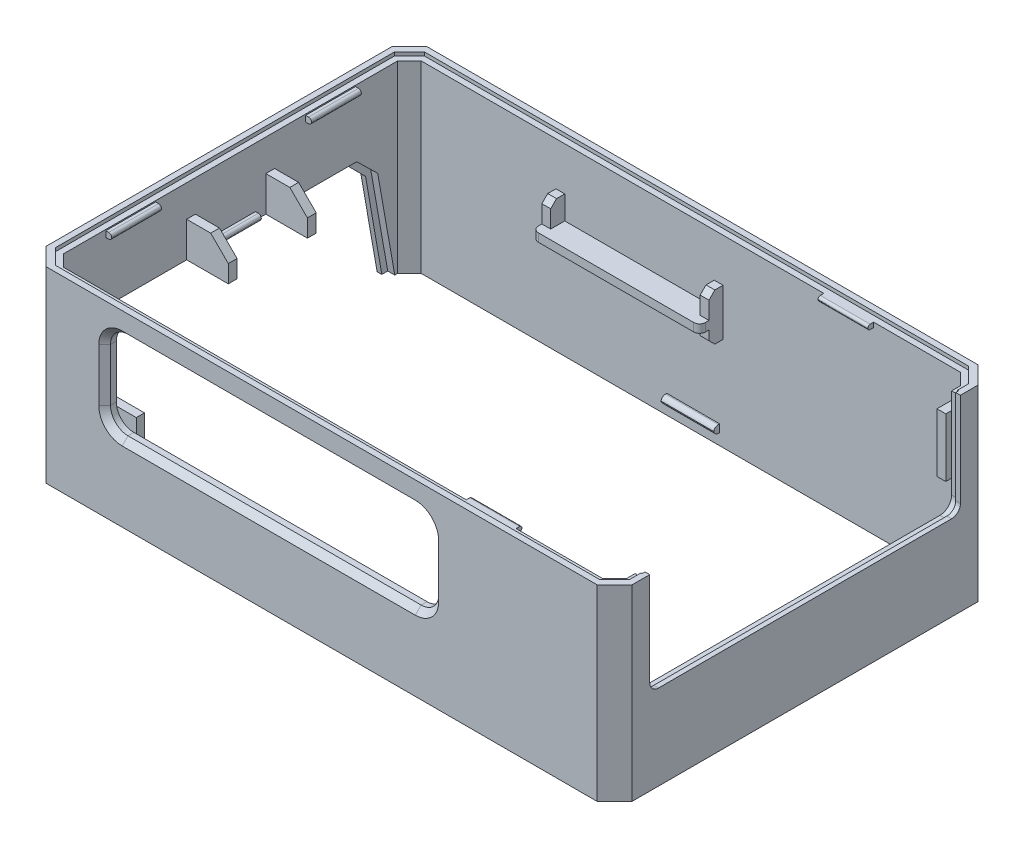
SolidWorks part; units mm, degrees
ref_plane "前视基准面" through (0, 0, 0) normal (0, 0, 1) x (1, 0, 0)
ref_plane "上视基准面" through (0, 0, 0) normal (0, 1, 0) x (1, 0, 0)
ref_plane "右视基准面" through (0, 0, 0) normal (1, 0, 0) x (0, 0, -1)
sketch "草图1" plane through (0, 0, 0) normal (0, 1, 0) x (1, 0, 0)
  line L1 (-50, 32.5) -> (50, 32.5)
  line L2 (-50, 32.5) -> (-50, -32.5)
  line L3 (-50, -32.5) -> (50, -32.5)
  line L4 (50, 32.5) -> (50, -32.5)
  line L5 (-50, 32.5) -> (50, -32.5) construction
  line L6 (-50, -32.5) -> (50, 32.5) construction
  point P0 (0, 0)
  dimension "D1" = 65
  dimension "D2" = 100
extrude "凸台-拉伸1" add sketch "草图1" along normal blind 32
sketch "草图2" plane through (0, 32, 0) normal (0, 1, 0) x (1, 0, 0)
  line L8 (48, -30.5) -> (48, 30.5)
  line L9 (48, 30.5) -> (-48, 30.5)
  line L10 (-48, 30.5) -> (-48, -30.5)
  line L11 (-48, -30.5) -> (48, -30.5)
  line L12 (48, -30.5) -> (48, 30.5)
  line L13 (48, 30.5) -> (-48, 30.5)
  line L14 (-48, 30.5) -> (-48, -30.5)
  line L15 (-48, -30.5) -> (48, -30.5)
  dimension "D1" = 2
extrude "切除-拉伸1" cut sketch "草图2" against normal through all
sketch "草图4" plane through (-50, 0, 0) normal (-1, 0, 0) x (0, 0, 1)
  line L0 (-32.5, 0) -> (32.5, 0) construction
  line L3 (-28, 0) -> (28, 0)
  line L7 (-25.0863, 16.5) -> (-21.5, 20)
  line L8 (21.5, 20) -> (25.09, 16.5)
  line L9 (32.5, 32) -> (32.5, 0) construction
  line L12 (-25.0863, 16.5) -> (-28, 0)
  line L13 (-21.5, 20) -> (21.5, 20)
  line L14 (25.09, 16.5) -> (28, 0)
  line L15 (-32.5, 0) -> (32.5, 0) construction
  line L16 (-32.5, 32) -> (-32.5, 0) construction
  dimension "D1" = 16.5
  dimension "D2" = 20
  dimension "D3" = 4.5
  dimension "D4" = 4.5
  dimension "D5" = 11
  dimension "D6" = 11
  dimension "D7" = 7.4137
  dimension "D8" = 7.41
extrude "切除-拉伸2" cut sketch "草图4" against normal blind 2
sketch "草图7" plane through (0, 0, 32.5) normal (0, 0, 1) x (1, 0, 0)
  line L16 (-37, 28) -> (-37, 13)
  line L17 (19, 28) -> (-37, 28)
  line L18 (19, 13) -> (19, 28)
  line L19 (-37, 13) -> (19, 13)
extrude "切除-拉伸3" cut sketch "草图7" against normal blind 2.5
fillet "圆角7" radius 3 4 edges at (-37, 28, 31.5) (19, 28, 31.5) (19, 13, 31.5) (-37, 13, 31.5)
chamfer "倒角1" distance 1 angle 45 8 edges at (-9, 28, 32.5) (-36.1213, 27.1213, 32.5) (18.1213, 27.1213, 32.5) (-37, 20.5, 32.5) (19, 20.5, 32.5) (-36.1213, 13.8787, 32.5) (18.1213, 13.8787, 32.5) (-9, 13, 32.5)
sketch "草图9" plane through (50, 0, 0) normal (1, 0, 0) x (0, 0, -1)
  line L0 (-25.6851, 37.094) -> (-12.3808, 37.094)
  line L1 (-25.6851, 37.094) -> (-25.6851, 22.8739)
  line L2 (-25.6851, 22.8739) -> (-12.3808, 22.8739)
  line L3 (-12.3808, 37.094) -> (-12.3808, 22.8739)
  line L4 (-7.5808, 37.094) -> (5.5192, 37.094)
  line L5 (-7.5808, 37.094) -> (-7.5808, 22.8739)
  line L6 (-7.5808, 22.8739) -> (5.5192, 22.8739)
  line L7 (5.5192, 37.094) -> (5.5192, 22.8739)
  line L8 (10, 33.8806) -> (25.4692, 33.8806)
  line L9 (10, 33.8806) -> (10, 21.8806)
  line L10 (10, 21.8806) -> (25.4692, 21.8806)
  line L11 (25.4692, 33.8806) -> (25.4692, 21.8806)
  line L14 (-32.5, 32) -> (-32.5, 0) construction
  line L15 (32.5, 32) -> (32.5, 0) construction
  dimension "D1" = 14.2201
  dimension "D2" = 13.1
  dimension "D3" = 6.8149
  dimension "D4" = 24.9192
  dimension "D5" = 7.0308
  dimension "D6" = 12
ref_plane "基准面4" through (0, 19.25, 0) normal (0, -1, 0) x (-1, 0, 0)
sketch "草图10" plane through (0, 19.25, 0) normal (0, -1, 0) x (-1, 0, 0)
  line L0 (-41.8403, 31.4577) -> (-41.8403, -31.3544)
sketch "草图11" plane through (48, 0, 0) normal (-1, 0, 0) x (0, 0, 1)
  line L1 (-8.8, 24.925) -> (-7.3, 24.925)
  line L2 (-8.8, 24.925) -> (-8.8, 19.925)
  line L3 (-8.8, 19.925) -> (-7.3, 19.925)
  line L4 (-7.3, 24.925) -> (-7.3, 19.925)
  line L5 (32.5, 32) -> (25.6851, 32) construction
  line L6 (9, 24.925) -> (10.5, 24.925)
  line L7 (9, 24.925) -> (9, 19.925)
  line L8 (9, 19.925) -> (10.5, 19.925)
  line L9 (10.5, 24.925) -> (10.5, 19.925)
  line L11 (32.5, 32) -> (32.5, 0) construction
  line L12 (-32.5, 32) -> (-32.5, 0) construction
  dimension "D1" = 1.5
  dimension "D2" = 1.5
  dimension "D3" = 22
  dimension "D4" = 23.7
  dimension "D5" = 5
  dimension "D6" = 12.075
sketch "草图17" plane through (-48, 0, 0) normal (1, 0, 0) x (0, 0, -1)
  line L1 (-6, 20) -> (-7.5, 20)
  line L2 (-6, 20) -> (-6, 26)
  line L3 (-6, 26) -> (-7.5, 26)
  line L4 (-7.5, 20) -> (-7.5, 26)
  line L5 (32.5, 32) -> (32.5, 0) construction
  line L6 (6, 20) -> (7.5, 20)
  line L7 (6, 20) -> (6, 26)
  line L8 (6, 26) -> (7.5, 26)
  line L9 (7.5, 20) -> (7.5, 26)
  line L10 (-21.5, 20) -> (21.5, 20) construction
  line L12 (-32.5, 32) -> (-32.5, 0) construction
  dimension "D1" = 1.5
  dimension "D2" = 1.5
  dimension "D3" = 25
  dimension "D4" = 25
  dimension "D5" = 6
extrude "凸台-拉伸6" add sketch "草图17" along normal blind 7.1
chamfer "倒角6" distance 3 angle 45 2 edges at (-40.9, 26, -6.75) (-40.9, 26, 6.75)
sketch "草图24" plane through (48, 0, 0) normal (-1, 0, 0) x (0, 0, 1)
  line L1 (-4.5, 3.3) -> (4.5, 3.3)
  line L2 (-4.5, 3.3) -> (-4.5, 1.8)
  line L3 (-4.5, 1.8) -> (4.5, 1.8)
  line L4 (4.5, 3.3) -> (4.5, 1.8)
  line L5 (-4.5, 3.3) -> (4.5, 1.8) construction
  line L6 (-4.5, 1.8) -> (4.5, 3.3) construction
  line L7 (30.5, 0) -> (-30.5, 0) construction
  line L8 (32.5, 0) -> (-32.5, 0) construction
  point P0 (0, 2.55)
  point P10 (0, 0)
  dimension "D1" = 1.5
  dimension "D2" = 1.8
  dimension "D3" = 9
extrude "凸台-拉伸10" add sketch "草图24" along normal blind 1
fillet "圆角15" radius 0.8 2 edges at (47, 3.3, 0) (47, 1.8, 0)
sketch "草图25" plane through (0, 0, 30.5) normal (0, 0, -1) x (-1, 0, 0)
  line L0 (48, 0) -> (-48, 0) construction
  line L1 (-4.9102, 3.2365) -> (4.0898, 3.2365)
  line L2 (-4.9102, 3.2365) -> (-4.9102, 1.9365)
  line L3 (-4.9102, 1.9365) -> (4.0898, 1.9365)
  line L4 (4.0898, 3.2365) -> (4.0898, 1.9365)
  line L5 (-4.9102, 3.2365) -> (4.0898, 1.9365) construction
  line L6 (-4.9102, 1.9365) -> (4.0898, 3.2365) construction
  line L8 (50, 32) -> (50, 0) construction
  point P0 (-0.4102, 2.5865)
  dimension "D1" = 9
  dimension "D2" = 1.3
  dimension "D3" = 2.5865
  dimension "D4" = 50.4102
extrude "凸台-拉伸11" add sketch "草图25" along normal blind 1
sketch "草图26" plane through (0, 0, -30.5) normal (0, 0, 1) x (1, 0, 0)
  line L4 (-4.0898, 3.2365) -> (-4.0898, 1.9365)
  line L5 (4.9102, 3.2365) -> (-4.0898, 3.2365)
  line L6 (4.9102, 1.9365) -> (4.9102, 3.2365)
  line L7 (-4.0898, 1.9365) -> (4.9102, 1.9365)
  line L8 (-4.0898, 3.2365) -> (-4.0898, 1.9365)
  line L9 (4.9102, 3.2365) -> (-4.0898, 3.2365)
  line L10 (4.9102, 1.9365) -> (4.9102, 3.2365)
  line L11 (-4.0898, 1.9365) -> (4.9102, 1.9365)
  dimension "D1" = 0
extrude "凸台-拉伸12" add sketch "草图26" along normal blind 1
fillet "圆角16" radius 0.8 4 edges at (0.4102, 1.9365, -29.5) (0.4102, 3.2365, -29.5) (0.4102, 1.9365, 29.5) (0.4102, 3.2365, 29.5)
chamfer "倒角7" distance 2 angle 45 4 edges at (-48, 16, -30.5) (-48, 16, 30.5) (48, 16, -30.5) (48, 16, 30.5)
chamfer "倒角8" distance 3 angle 45 4 edges at (-50, 16, 32.5) (-50, 16, -32.5) (50, 16, -32.5) (50, 16, 32.5)
sketch "草图28" plane through (-50, 0, 0) normal (-1, 0, 0) x (0, 0, 1)
  line L27 (-29.3, 22.3393) -> (-29.3, 0)
  line L28 (-29.3, 0) -> (-26.9872, 0)
  line L29 (-26.9872, 0) -> (-24.2154, 15.8784)
  line L30 (-24.2154, 15.8784) -> (-21.1176, 18.9896)
  line L31 (-21.1176, 18.9896) -> (21.1176, 18.9896)
  line L32 (21.1176, 18.9896) -> (24.2152, 15.8784)
  line L33 (24.2152, 15.8784) -> (27.008, 0)
  line L34 (27.008, 0) -> (29.3, 0)
  line L35 (29.3, 0) -> (29.3, 22.3393)
  line L36 (29.3, 22.3393) -> (-29.3, 22.3393)
  line L37 (28.5, 0) -> (-28.5, 0) construction
  line L38 (-29.5, 0) -> (-28, 0) construction
  line L39 (28, 0) -> (29.5, 0) construction
extrude "凸台-拉伸13" add sketch "草图28" against normal blind 0.8
sketch "草图30" plane through (-50, 0, 0) normal (-1, 0, 0) x (0, 0, 1)
  line L20 (27.008, 0) -> (29.5, 0) construction
  line L21 (-29.5, 0) -> (-26.9872, 0) construction
  line L22 (-29.5, 32) -> (-29.5, 0) construction
  line L23 (29.5, 0) -> (29.5, 32) construction
  line L24 (-29.5, 32) -> (29.5, 32) construction
  line L32 (27.58, 0) -> (24.7738, 16.1781)
  line L33 (24.7738, 16.1781) -> (21.3669, 19.6)
  line L34 (21.3669, 19.6) -> (-21.3669, 19.6)
  line L35 (-21.3669, 19.6) -> (-24.7741, 16.1781)
  line L36 (-24.7741, 16.1781) -> (-27.5845, 0)
  dimension "D1" = 1.9155
  dimension "D2" = 1.92
  dimension "D3" = 4.7262
  dimension "D4" = 8.1331
  dimension "D5" = 4.7259
  dimension "D6" = 8.1331
  dimension "D7" = 12.4
  dimension "D8" = 15.8219
sketch "草图35" plane through (48, 0, 0) normal (-1, 0, 0) x (0, 0, 1)
  line L0 (-27, 32) -> (27, 32)
  line L1 (-27, 32) -> (-27, 14)
  line L2 (-27, 14) -> (27, 14)
  line L3 (27, 32) -> (27, 14)
  line L4 (32.5, 0) -> (32.5, 32) construction
  line L5 (-32.5, 32) -> (-32.5, 0) construction
  line L6 (28.5, 32) -> (-28.5, 32) construction
  dimension "D1" = 18
  dimension "D3" = 5.5
  dimension "D4" = 5.5
extrude "切除-拉伸6" cut sketch "草图35" against normal blind 1.2
fillet "圆角17" radius 2 2 edges at (48.6, 14, -27) (48.6, 14, 27)
sketch "草图39" plane through (49.2, 0, 0) normal (-1, 0, 0) x (0, 0, 1)
  line L2 (27, 32) -> (-27, 32) construction
  line L12 (-26.5, 32) -> (-26.5, 16)
  line L13 (-25, 14.5) -> (25, 14.5)
  line L14 (26.5, 16) -> (26.5, 32)
  line L15 (26.5, 32) -> (-26.5, 32)
  arc A6 (-26.5, 16) -> (-25, 14.5) centre (-25, 16) ccw
  arc A7 (25, 14.5) -> (26.5, 16) centre (25, 16) ccw
extrude "切除-拉伸7" cut sketch "草图39" against normal blind 1.2
ref_plane "基准面5" through (-50, 32, 29.5) normal (0.7071, 0, 0.7071) x (0.7071, 0, -0.7071)
sketch "草图42" plane through (-48, 0, 0) normal (1, 0, 0) x (0, 0, -1)
  line L0 (32.5, 0) -> (32.5, 32) construction
  line L1 (12.8, 31.2) -> (21.3, 31.2)
  line L2 (12.8, 31.2) -> (12.8, 30.2)
  line L3 (12.8, 30.2) -> (21.3, 30.2)
  line L4 (21.3, 31.2) -> (21.3, 30.2)
  line L5 (12.8, 31.2) -> (21.3, 30.2) construction
  line L6 (12.8, 30.2) -> (21.3, 31.2) construction
  line L7 (-4.2291, 21.2667) -> (4.2291, 21.2667)
  line L8 (-4.2291, 21.2667) -> (-4.2291, 20.2667)
  line L9 (-4.2291, 20.2667) -> (4.2291, 20.2667)
  line L10 (4.2291, 21.2667) -> (4.2291, 20.2667)
  line L11 (-4.2291, 21.2667) -> (4.2291, 20.2667) construction
  line L12 (-4.2291, 20.2667) -> (4.2291, 21.2667) construction
  line L13 (-32.5, 32) -> (-32.5, 0) construction
  line L14 (28.5, 32) -> (-28.5, 32) construction
  line L15 (-12.8, 30.2) -> (-21.3, 30.2)
  line L16 (-12.8, 30.2) -> (-12.8, 31.2)
  line L17 (-12.8, 31.2) -> (-21.3, 31.2)
  line L18 (-21.3, 30.2) -> (-21.3, 31.2)
  line L19 (-12.8, 30.2) -> (-21.3, 31.2) construction
  line L20 (-12.8, 31.2) -> (-21.3, 30.2) construction
  point P0 (17.05, 30.7)
  point P5 (0, 20.7667)
  point P16 (-17.05, 30.7)
  dimension "D1" = 1
  dimension "D2" = 1
  dimension "D3" = 1.3
  dimension "D4" = 11.2
  dimension "D5" = 8.5
  dimension "D6" = 1
  dimension "D7" = 8.5
  dimension "D8" = 11.2
  dimension "D9" = 1.3
extrude "凸台-拉伸14" add sketch "草图42" along normal blind 1
fillet "圆角18" radius 0.5 6 edges at (-47, 20.2667, 0) (-47, 21.2667, 0) (-47, 30.2, -17.05) (-47, 31.2, -17.05) (-47, 31.2, 17.05) (-47, 30.2, 17.05)
sketch "草图44" plane through (0, 0, -27) normal (0, 0, 1) x (1, 0, 0)
  line L0 (48, 32) -> (48, 16) construction
  line L1 (48, 28.5) -> (46.5, 28.5)
  line L2 (48, 28.5) -> (48, 18.5)
  line L3 (48, 18.5) -> (46.5, 18.5)
  line L4 (46.5, 28.5) -> (46.5, 18.5)
  line L5 (50, 14.5) -> (49.2, 14.5) construction
  dimension "D1" = 1.5
  dimension "D2" = 10
  dimension "D3" = 4
extrude "凸台-拉伸15" add sketch "草图44" along normal blind 1 and the other way up to surface (3.5 mm away) other way up to face at (0, 16, -30.5)
sketch "草图45" plane through (0, 0, 27) normal (0, 0, -1) x (-1, 0, 0)
  line L4 (-48, 28.5) -> (-48, 18.5)
  line L5 (-46.5, 28.5) -> (-48, 28.5)
  line L6 (-46.5, 18.5) -> (-46.5, 28.5)
  line L7 (-48, 18.5) -> (-46.5, 18.5)
  line L8 (-48, 28.5) -> (-48, 18.5)
  line L9 (-46.5, 28.5) -> (-48, 28.5)
  line L10 (-46.5, 18.5) -> (-46.5, 28.5)
  line L11 (-48, 18.5) -> (-46.5, 18.5)
  dimension "D1" = 0
extrude "凸台-拉伸16" add sketch "草图45" along normal blind 1 and the other way up to surface (3.5 mm away) other way up to face at (0, 16, 30.5)
ref_plane "基准面6" through (48, 0, -28.5) normal (0, 0, -1) x (-1, 0, 0)
sketch "草图48" plane through (0, 32, 0) normal (0, 1, 0) x (1, 0, 0)
  line L0 (48, 28.5) -> (46, 30.5)
  line L1 (46, 30.5) -> (-46, 30.5)
  line L2 (48, 28.5) -> (48, -28.5)
  line L3 (46, -30.5) -> (-46, -30.5)
  line L4 (-48, 28.5) -> (-48, -28.5)
  line L5 (48, -28.5) -> (46, -30.5)
  line L6 (-46, -30.5) -> (-48, -28.5)
  line L7 (-46, 30.5) -> (-48, 28.5)
  line L8 (49, 28.9142) -> (49, -28.9142)
  line L9 (49, -28.9142) -> (46.4142, -31.5)
  line L10 (46.4142, -31.5) -> (-46.4142, -31.5)
  line L11 (-46.4142, -31.5) -> (-49, -28.9142)
  line L12 (-49, 28.9142) -> (-49, -28.9142)
  line L13 (-46.4142, 31.5) -> (-49, 28.9142)
  line L14 (46.4142, 31.5) -> (-46.4142, 31.5)
  line L15 (49, 28.9142) -> (46.4142, 31.5)
  point P0 (48, 30.5)
  point P1 (-48, -30.5)
  point P2 (48, -30.5)
  point P3 (-48, 30.5)
  dimension "D2" = 1
extrude "切除-拉伸8" cut sketch "草图48" against normal blind 0.6
sketch "草图49" plane through (0, 0, -30.5) normal (0, 0, 1) x (1, 0, 0)
  line L0 (50, 32) -> (50, 16) construction
  line L1 (22.6985, 31.4) -> (31.1985, 31.4)
  line L2 (22.6985, 31.4) -> (22.6985, 30.6)
  line L3 (22.6985, 30.6) -> (31.1985, 30.6)
  line L4 (31.1985, 31.4) -> (31.1985, 30.6)
  line L5 (22.6985, 31.4) -> (31.1985, 30.6) construction
  line L6 (22.6985, 30.6) -> (31.1985, 31.4) construction
  line L7 (46, 31.4) -> (-46, 31.4) construction
  point P0 (26.9485, 31)
  dimension "D1" = 0.8
  dimension "D2" = 8.5
  dimension "D3" = 18.8015
extrude "凸台-拉伸17" add sketch "草图49" along normal blind 1
sketch "草图50" plane through (0, 0, 30.5) normal (0, 0, -1) x (-1, 0, 0)
  line L4 (-31.1985, 31.4) -> (-31.1985, 30.6)
  line L5 (-22.6985, 31.4) -> (-31.1985, 31.4)
  line L6 (-22.6985, 30.6) -> (-22.6985, 31.4)
  line L7 (-31.1985, 30.6) -> (-22.6985, 30.6)
  line L8 (-31.1985, 31.4) -> (-31.1985, 30.6)
  line L9 (-22.6985, 31.4) -> (-31.1985, 31.4)
  line L10 (-22.6985, 30.6) -> (-22.6985, 31.4)
  line L11 (-31.1985, 30.6) -> (-22.6985, 30.6)
  dimension "D1" = 0
extrude "凸台-拉伸18" add sketch "草图50" along normal blind 1
fillet "圆角20" radius 0.4 4 edges at (26.9485, 31.4, 29.5) (26.9485, 30.6, 29.5) (26.9485, 31.4, -29.5) (26.9485, 30.6, -29.5)
sketch "草图51" plane through (0, 0, 30.5) normal (0, 0, -1) x (-1, 0, 0)
  line L0 (35.1966, 7.8) -> (35.1966, 9.1168)
  line L1 (-21, 13.8) -> (-22.5, 13.8)
  line L3 (-17, 7.8) -> (-22.5, 7.8)
  line L4 (-22.5, 13.8) -> (-22.5, 7.8)
  line L5 (46, 0) -> (-46, 0) construction
  line L6 (-17, 7.8) -> (-17, 9.1168)
  line L7 (-17, 9.1168) -> (-21, 9.1168)
  line L8 (-21, 9.1168) -> (-21, 13.8)
  line L9 (35.1966, 9.1168) -> (39.1966, 9.1168)
  line L10 (40.6966, 13.8) -> (39.1966, 13.8)
  line L11 (40.6966, 13.8) -> (40.6966, 7.8)
  line L12 (40.6966, 7.8) -> (35.1966, 7.8)
  line L13 (39.1966, 9.1168) -> (39.1966, 13.8)
  line L14 (50, 0) -> (50, 32) construction
  line L15 (-50, 32) -> (-50, 0) construction
  dimension "D1" = 1.5
  dimension "D2" = 6
  dimension "D3" = 1.5
  dimension "D4" = 7.8
  dimension "D5" = 6
  dimension "D6" = 5.5
  dimension "D7" = 9.3034
  dimension "D8" = 27.5
  dimension "D9" = 5.5
extrude "凸台-拉伸19" add sketch "草图51" along normal blind 3
sketch "草图52" plane through (21, 0, 0) normal (-1, 0, 0) x (0, 0, 1)
  line L0 (27.5, 9.1168) -> (27.5, 13.8) construction
  line L1 (27.5, 13.8) -> (28.9, 13.8)
  line L2 (27.5, 13.8) -> (27.5, 9.1168)
  line L3 (27.5, 9.1168) -> (28.9, 9.1168)
  line L4 (28.9, 13.8) -> (28.9, 9.1168)
  line L5 (27.5, 13.8) -> (30.5, 13.8) construction
  line L6 (27.5, 9.1168) -> (30.5, 9.1168) construction
  dimension "D1" = 1.4
extrude "凸台-拉伸20" add sketch "草图52" along normal blind 4
sketch "草图53" plane through (-39.1966, 0, 0) normal (1, 0, 0) x (0, 0, -1)
  line L4 (-27.5, 7.8) -> (-27.5, 13.8)
  line L5 (-28.9, 9.1168) -> (-30.5, 9.1168)
  line L6 (-28.9, 13.8) -> (-28.9, 9.1168)
  line L7 (-27.5, 13.8) -> (-28.9, 13.8)
  line L8 (-27.5, 7.8) -> (-27.5, 13.8)
  line L9 (-28.9, 9.1168) -> (-30.5, 9.1168)
  line L10 (-28.9, 13.8) -> (-28.9, 9.1168)
  line L11 (-27.5, 13.8) -> (-28.9, 13.8)
  line L14 (-30.5, 9.1168) -> (-30.5, 7.8)
  line L15 (-30.5, 9.1168) -> (-30.5, 7.8)
  line L16 (-30.5, 7.8) -> (-27.5, 7.8)
  line L17 (-30.5, 7.8) -> (-27.5, 7.8)
  dimension "D1" = 0
extrude "凸台-拉伸21" add sketch "草图53" along normal blind 4
sketch "草图55" plane through (0, 0, -30.5) normal (0, 0, 1) x (1, 0, 0)
  line L0 (-50, 0) -> (-50, 32) construction
  line L1 (-23, 20) -> (5.5, 20)
  line L2 (-23, 20) -> (-23, 18.6)
  line L3 (-23, 18.6) -> (5.5, 18.6)
  line L4 (5.5, 20) -> (5.5, 18.6)
  line L5 (-47, 32) -> (47, 32) construction
  dimension "D1" = 1.4
  dimension "D2" = 27
  dimension "D3" = 12
  dimension "D4" = 28.5
extrude "凸台-拉伸22" add sketch "草图55" along normal blind 4
sketch "草图56" plane through (0, 0, -30.5) normal (0, 0, 1) x (1, 0, 0)
  line L0 (-50, 0) -> (-50, 32) construction
  line L1 (-23, 24) -> (-21.5, 24)
  line L2 (-23, 24) -> (-23, 16)
  line L3 (-23, 16) -> (-21.5, 16)
  line L4 (-21.5, 24) -> (-21.5, 16)
  line L5 (4, 24) -> (5.5, 24)
  line L6 (4, 24) -> (4, 16)
  line L7 (4, 16) -> (5.5, 16)
  line L8 (5.5, 24) -> (5.5, 16)
  line L9 (-47, 32) -> (47, 32) construction
  dimension "D1" = 1.5
  dimension "D2" = 8
  dimension "D3" = 27
  dimension "D4" = 54
  dimension "D5" = 8
extrude "凸台-拉伸23" add sketch "草图56" along normal blind 2.4
chamfer "倒角9" distance 1 angle 45 4 edges at (-22.25, 16, -28.1) (4.75, 16, -28.1) (4.75, 24, -28.1) (-22.25, 24, -28.1)
fillet "圆角21" radius 1 2 edges at (5.5, 19.3, -26.5) (-23, 19.3, -26.5)
